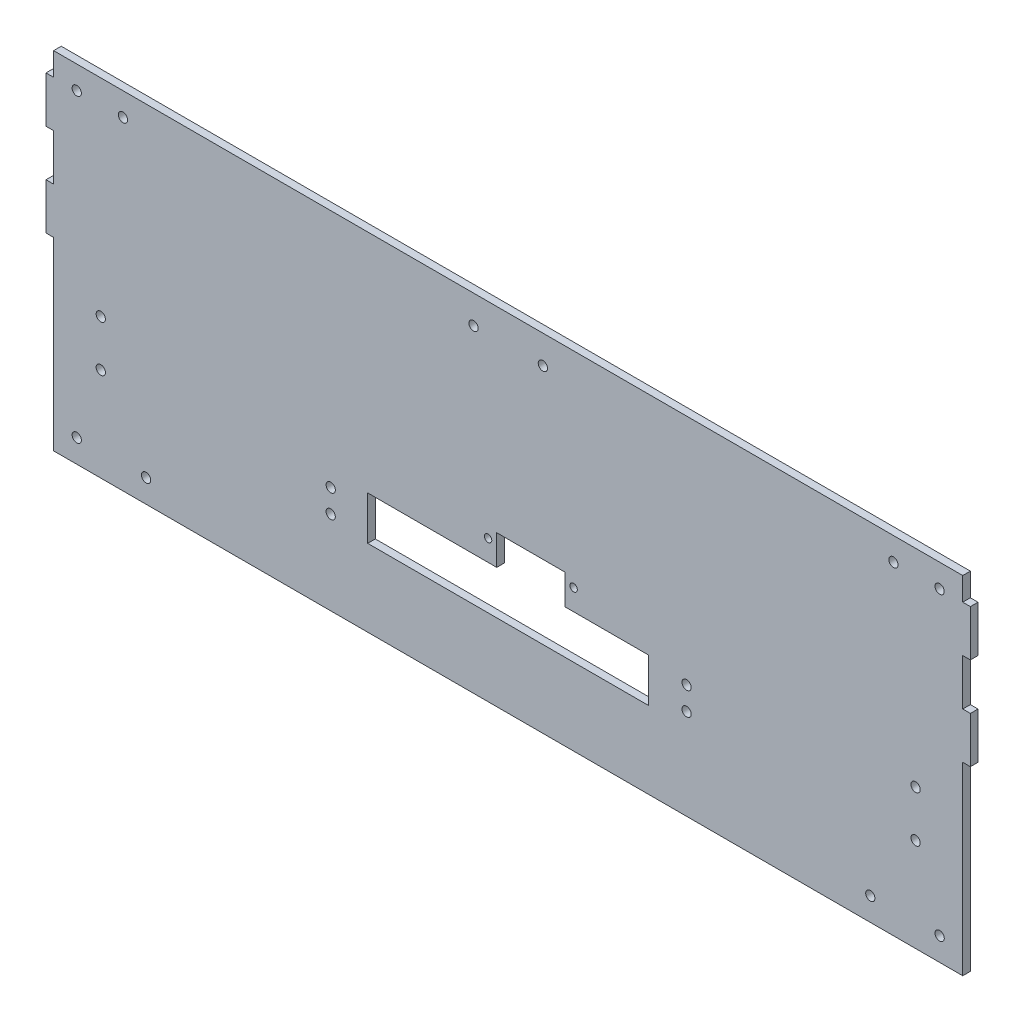
SolidWorks part; units mm, degrees
material "Balsa"
ref_plane "Front Plane" through (0, 0, 0) normal (0, 0, 1) x (1, 0, 0)
ref_plane "Top Plane" through (0, 0, 0) normal (0, 1, 0) x (1, 0, 0)
ref_plane "Right Plane" through (0, 0, 0) normal (1, 0, 0) x (0, 0, -1)
sketch "Sketch1" plane through (0, 0, 0) normal (0, 0, 1) x (1, 0, 0)
  line L0 (223.7, 24.5) -> (223.7, -237.7) construction
  line L1 (-169.7, 24.5) -> (223.7, 24.5)
  line L2 (-169.7, 24.5) -> (-169.7, -125.5)
  line L3 (-169.7, -125.5) -> (223.7, -125.5)
  line L4 (223.7, 24.5) -> (223.7, -125.5)
  line L5 (-169.7, 24.5) -> (223.7, -125.5) construction
  line L6 (-169.7, -125.5) -> (223.7, 24.5) construction
  line L7 (-169.7, -237.7) -> (-169.7, 24.5) construction
  line L8 (-173, 24.5) -> (227, 24.5) construction
  point P4 (27, -50.5)
  dimension "D1" = 150
extrude "Boss-Extrude1" add sketch "Sketch1" along normal blind 3.3
sketch "Sketch2" plane through (0, 0, 0) normal (0, 0, -1) x (-1, 0, 0)
  circle A0 centre (-183.7, -115.5) radius 2
  circle A1 centre (-213.7, -115.5) radius 2
  circle A2 centre (129.7, -115.5) radius 2
  circle A3 centre (159.7, -115.5) radius 2
  dimension "D1" = 4
  dimension "D2" = 4
  dimension "D3" = 4
  dimension "D4" = 4
extrude "Cut-Extrude1" cut sketch "Sketch2" against normal through all
sketch "Sketch3" plane through (0, 0, 3.3) normal (0, 0, 1) x (1, 0, 0)
  line L0 (-169.7, 24.5) -> (-169.7, -125.5) construction
  line L1 (223.7, 24.5) -> (-169.7, 24.5) construction
  line L2 (27, 24.5) -> (27, -125.5) construction
  line L3 (-169.7, -125.5) -> (223.7, -125.5) construction
  circle A0 centre (-159.7, 14.5) radius 2
  circle A1 centre (-139.7, 14.5) radius 2
  circle A2 centre (193.7, 14.5) radius 2
  circle A3 centre (213.7, 14.5) radius 2
  dimension "D1" = 4
  dimension "D2" = 4
  dimension "D3" = 20
  dimension "D4" = 10
  dimension "D5" = 10
  dimension "D6" = 10
extrude "Cut-Extrude2" cut sketch "Sketch3" against normal blind 4
sketch "Sketch4" plane through (0, 0, 3.3) normal (0, 0, 1) x (1, 0, 0)
  line L0 (223.7, 24.5) -> (-169.7, 24.5) construction
  line L1 (0, 24.5) -> (54, 24.5) construction
  line L2 (0, 24.5) -> (0, 0) construction
  line L3 (0, 0) -> (54, 0) construction
  line L4 (54, 24.5) -> (54, 0) construction
  line L5 (0, 24.5) -> (54, 0) construction
  line L6 (0, 0) -> (54, 24.5) construction
  line L7 (0, 24.5) -> (0, 0) construction
  line L8 (54, 0) -> (54, 24.5) construction
  line L9 (27, 24.5) -> (27, 0) construction
  circle A0 centre (12, 12.25) radius 2
  circle A2 centre (42, 12.25) radius 2
  point P4 (27, 12.25)
  dimension "D1" = 4
  dimension "D2" = 15
  dimension "D3" = 12.25
extrude "Cut-Extrude3" cut sketch "Sketch4" against normal blind 4
sketch "Sketch6" plane through (0, 0, 0) normal (0, 0, -1) x (-1, 0, 0)
  line L1 (-51.55, -60.2924) -> (-22.05, -60.2924)
  line L2 (-51.55, -60.2924) -> (-51.55, -73.2924)
  line L3 (-51.55, -73.2924) -> (-22.05, -73.2924)
  line L4 (-22.05, -60.2924) -> (-22.05, -73.2924)
  line L5 (-51.55, -60.2924) -> (-22.05, -73.2924) construction
  line L6 (-51.55, -73.2924) -> (-22.05, -60.2924) construction
  line L7 (-87.7897, -73.2924) -> (33.7897, -73.2924)
  line L8 (-87.7897, -73.2924) -> (-87.7897, -92.1924)
  line L9 (-87.7897, -92.1924) -> (33.7897, -92.1924)
  line L10 (33.7897, -73.2924) -> (33.7897, -92.1924)
  line L11 (-87.7897, -73.2924) -> (33.7897, -92.1924) construction
  line L12 (-87.7897, -92.1924) -> (33.7897, -73.2924) construction
  line L15 (-223.7, -125.5) -> (-223.7, 24.5) construction
  line L16 (169.7, -125.5) -> (-223.7, -125.5) construction
  point P4 (-36.8, -79)
  point P11 (-27, -97.7424)
  dimension "D1" = 18.9
  dimension "D2" = 0
  dimension "D3" = 121.5794
  dimension "D4" = 55.8397
  dimension "D5" = 13
  dimension "D6" = 29.5
  dimension "D7" = 135.9103
  dimension "D8" = 33.3076
extrude "Cut-Extrude4" cut sketch "Sketch6" against normal blind 10 contours L10 L7 L3 L8 L9 | L4 L1 L2 L3 region at (36.8, -66.7924, 0) region at (27, -82.7424, 0)
sketch "Sketch7" plane through (0, 0, 3.3) normal (0, 0, 1) x (1, 0, 0)
  circle A0 centre (-149.2981, -64.95) radius 2
  circle A1 centre (-149.2981, -84.95) radius 2
  circle A2 centre (-49.7979, -89.2424) radius 2
  circle A3 centre (-49.7979, -79.2424) radius 2
  circle A4 centre (18.3, -64.2269) radius 1.6
  circle A5 centre (55.3, -64.2269) radius 1.6
  circle A6 centre (104.2014, -76.2424) radius 2
  circle A7 centre (104.2014, -86.2424) radius 2
  circle A10 centre (-149.2981, -64.95) radius 2 construction
  circle A11 centre (-149.2981, -84.95) radius 2 construction
  circle A12 centre (-49.7979, -79.2424) radius 2 construction
  circle A13 centre (-49.7979, -89.2424) radius 2 construction
  circle A14 centre (18.3, -64.2269) radius 1.6 construction
  circle A15 centre (55.3, -64.2269) radius 1.6 construction
  circle A16 centre (104.2014, -76.2424) radius 2 construction
  circle A17 centre (104.2014, -86.2424) radius 2 construction
  circle A20 centre (203.2981, -84.9682) radius 2
  circle A21 centre (203.2981, -64.9682) radius 2
  circle A22 centre (203.2981, -84.9682) radius 2 construction
  circle A23 centre (203.2981, -64.9682) radius 2 construction
extrude "Cut-Extrude5" cut sketch "Sketch7" against normal blind 10
sketch "Sketch8" plane through (0, 0, 3.3) normal (0, 0, 1) x (1, 0, 0)
  line L0 (-169.7, 24.5) -> (-169.7, -125.5) construction
  line L1 (-169.7, 14.5) -> (-173, 14.5)
  line L2 (-169.7, 14.5) -> (-169.7, -5.5)
  line L3 (-169.7, -5.5) -> (-173, -5.5)
  line L4 (-173, 14.5) -> (-173, -5.5)
  line L5 (-169.7, 14.5) -> (-173, -5.5) construction
  line L6 (-169.7, -5.5) -> (-173, 14.5) construction
  line L7 (223.7, -125.5) -> (223.7, 24.5) construction
  line L8 (-169.7, -25.5304) -> (-173, -25.5304)
  line L9 (-169.7, -25.5304) -> (-169.7, -45.5)
  line L10 (-169.7, -45.5) -> (-173, -45.5)
  line L11 (-173, -25.5304) -> (-173, -45.5)
  line L12 (-169.7, -25.5304) -> (-173, -45.5) construction
  line L13 (-169.7, -45.5) -> (-173, -25.5304) construction
  line L14 (223.7, -25.5304) -> (227, -25.5304)
  line L15 (223.7, -25.5304) -> (223.7, -45.5)
  line L16 (223.7, -45.5) -> (227, -45.5)
  line L17 (227, -25.5304) -> (227, -45.5)
  line L18 (223.7, -25.5304) -> (227, -45.5) construction
  line L19 (223.7, -45.5) -> (227, -25.5304) construction
  line L21 (223.7, -5.5) -> (227, -5.5)
  line L22 (223.7, -5.5) -> (223.7, 14.5)
  line L23 (223.7, 14.5) -> (227, 14.5)
  line L24 (227, -5.5) -> (227, 14.5)
  line L25 (223.7, -5.5) -> (227, 14.5) construction
  line L26 (223.7, 14.5) -> (227, -5.5) construction
  point P4 (-171.35, 4.5)
  point P11 (-171.35, -35.5152)
  point P16 (225.35, -35.5152)
  point P23 (225.35, 4.5)
extrude "Boss-Extrude2" add sketch "Sketch8" against normal blind 3.3
